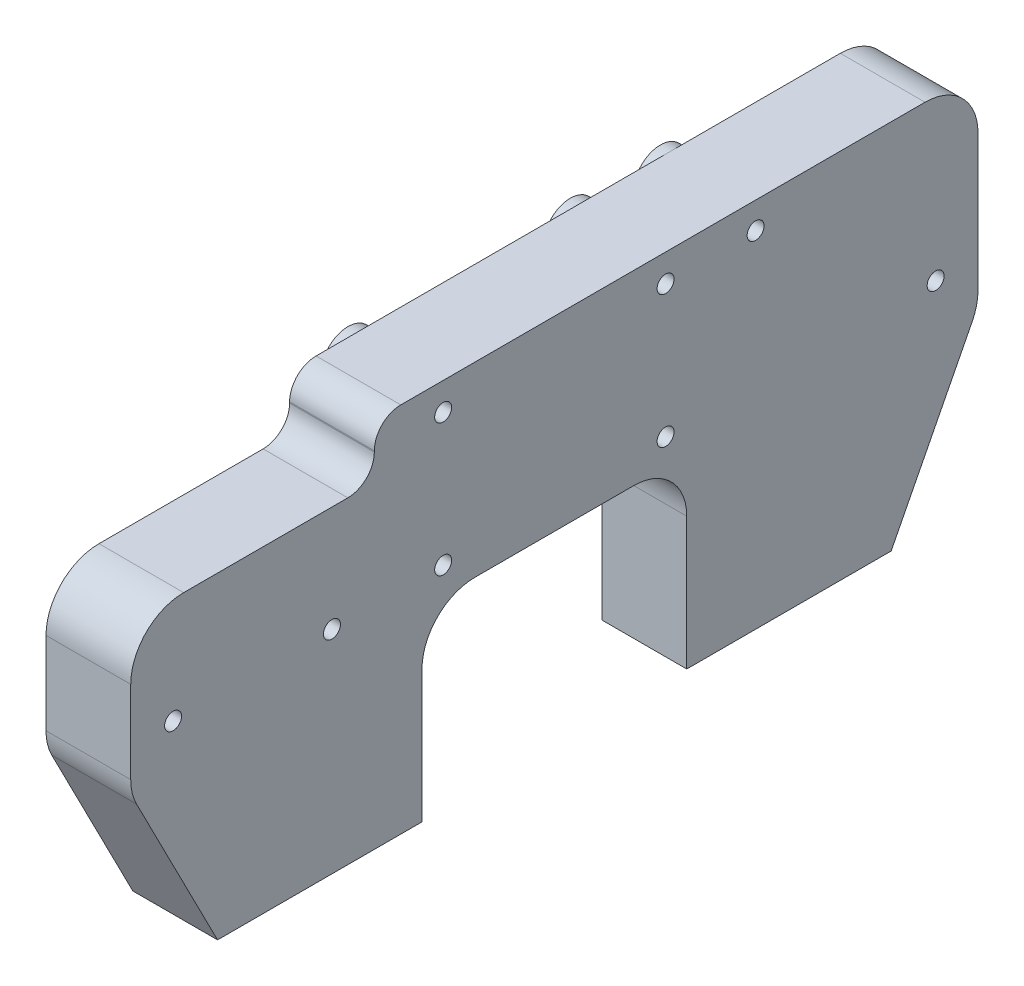
SolidWorks part; units mm, degrees
ref_plane "Front Plane" through (0, 0, 0) normal (0, 0, 1) x (1, 0, 0)
ref_plane "Top Plane" through (0, 0, 0) normal (0, 1, 0) x (1, 0, 0)
ref_plane "Right Plane" through (0, 0, 0) normal (1, 0, 0) x (0, 0, -1)
sketch "Sketch2" plane through (0, 0, 0) normal (1, 0, 0) x (0, 0, -1)
  line L0 (-40, 0) -> (-40, 40)
  line L1 (-40, 40) -> (40, 40)
  line L2 (40, 40) -> (40, 0)
  line L3 (40, 0) -> (-40, 0)
  point P4 (0, 0)
  dimension "D1" = 80
  dimension "D2" = 40
extrude "Boss-Extrude1" add sketch "Sketch2" along normal blind 8
sketch "Sketch3" plane through (8, 0, 0) normal (1, 0, 0) x (0, 0, -1)
  line L0 (-40, 40) -> (-40, 0) construction
  line L1 (-38.5, 17.5) -> (-18.5, 17.5) construction
  line L2 (-38.5, 17.5) -> (-38.5, 35.5) construction
  line L3 (-38.5, 35.5) -> (-18.5, 35.5) construction
  line L4 (-18.5, 17.5) -> (-18.5, 35.5) construction
  line L5 (-40, 0) -> (40, 0) construction
  circle A0 centre (-36, 20) radius 2.5
  circle A1 centre (-21, 20) radius 2.5
  point P4 (-28.5, 17.5)
  dimension "D1" = 5
  dimension "D2" = 5
  dimension "D3" = 15
  dimension "D4" = 20
  dimension "D5" = 18
  dimension "D6" = 7.5
  dimension "D7" = 2.5
  dimension "D8" = 4
  dimension "D9" = 20
extrude "Boss-Extrude2" add sketch "Sketch3" against normal blind 9 contours A0 | A1 region at (8, 20, 36) region at (8, 20, 21)
sketch "Sketch4" plane through (8, 0, 0) normal (1, 0, 0) x (0, 0, -1)
  line L0 (-40, 0) -> (40, 0) construction
  line L1 (16.5, 17.5) -> (38.5, 17.5)
  line L2 (16.5, 17.5) -> (16.5, 37.4)
  line L3 (16.5, 37.4) -> (38.5, 37.4)
  line L4 (38.5, 17.5) -> (38.5, 37.4)
  circle A0 centre (36, 20) radius 2.5
  circle A1 centre (19, 32.6) radius 2.5
  dimension "D1" = 5
  dimension "D2" = 5
  dimension "D3" = 12.6
  dimension "D4" = 17
  dimension "D5" = 19.9
  dimension "D6" = 22
  dimension "D7" = 20
extrude "Boss-Extrude3" add sketch "Sketch4" against normal blind 9 contours A0 | A1 region at (8, 32.6, -19) region at (8, 20, -36)
sketch "Sketch5" plane through (8, 0, 0) normal (1, 0, 0) x (0, 0, -1)
  line L1 (-12.5, 18) -> (12.5, 18) construction
  line L2 (-12.5, 18) -> (-12.5, 42) construction
  line L3 (-12.5, 42) -> (12.5, 42) construction
  line L4 (12.5, 18) -> (12.5, 42) construction
  line L5 (-40, 0) -> (40, 0) construction
  line L8 (40, 40) -> (-40, 40) construction
  circle A0 centre (-10.5, 20) radius 2.5
  circle A1 centre (10.5, 20) radius 2.5
  circle A2 centre (10.5, 32.5) radius 2.5
  circle A3 centre (-10.5, 32.5) radius 2.5
  point P3 (0, 42)
  point P17 (0, 40)
  dimension "D1" = 5
  dimension "D4" = 21
  dimension "D5" = 12.5
  dimension "D6" = 24
  dimension "D7" = 25
  dimension "D8" = 2
  dimension "D9" = 2
  dimension "D10" = 20
  dimension "D2" = 2
  dimension "D3" = 2
extrude "Boss-Extrude4" add sketch "Sketch5" against normal blind 9
sketch "Sketch7" plane through (8, 0, 0) normal (1, 0, 0) x (0, 0, -1)
  line L0 (-31.8, 0) -> (-40, 16)
  line L1 (-40, 0) -> (40, 0) construction
  line L2 (-40, 40) -> (-40, 0) construction
  line L3 (-40, 16) -> (-47.0872, 13.4851)
  line L4 (-47.0872, 13.4851) -> (-40, -21.9083)
  line L5 (-40, -21.9083) -> (60.4332, -20.413)
  line L6 (60.4332, -20.413) -> (53.6454, 13.4851)
  line L7 (53.6454, 13.4851) -> (40, 16)
  line L8 (40, 0) -> (40, 40) construction
  line L9 (40, 16) -> (31.8, 0)
  line L10 (-31.8, 0) -> (-12.5, 0)
  line L11 (-12.5, 0) -> (-12.5, 17.5)
  line L12 (-12.5, 17.5) -> (12.5, 17.5)
  line L13 (12.5, 17.5) -> (12.5, 0)
  line L14 (12.5, 0) -> (31.8, 0)
  line L15 (-40, 30) -> (-17, 30)
  line L16 (-17, 35.1) -> (-17, 30)
  line L17 (-17, 56.378) -> (-45.8801, 54.4436)
  line L18 (-45.8801, 54.4436) -> (-40, 30)
  line L19 (40, 35.1) -> (-17, 35.1)
  line L20 (-17, 44.251) -> (-17, 56.378)
  line L21 (-17, 44.251) -> (58.9628, 50.4661)
  line L22 (58.9628, 50.4661) -> (40, 35.1)
  circle A0 centre (-36, 20) radius 2.5 construction
  circle A1 centre (10.5, 20) radius 2.5 construction
  circle A2 centre (-21, 20) radius 2.5 construction
  circle A3 centre (19, 32.6) radius 2.5 construction
  point P15 (0, 17.5)
  point P22 (0, 0)
  dimension "D1" = 63.6
  dimension "D2" = 4
  dimension "D3" = 25
  dimension "D4" = 2.5
  dimension "D5" = 10
  dimension "D8" = 2.5
extrude "Cut-Extrude1" cut sketch "Sketch7" against normal through all
ref_plane "Plane1" through (4, 0, 0) normal (1, 0, 0) x (0, 0, -1)
fillet "Fillet5" radius 5 6 edges at (4, 16, -40) (4, 35.1, -40) (4, 30, 40) (4, 16, 40) (4, 17.5, -12.5) (4, 17.5, 12.5)
fillet "Fillet6" radius 2.5 2 edges at (4, 35.1, 17) (4, 30, 17)
sketch "Sketch8" plane through (0, 0, 0) normal (0, 1, 0) x (1, 0, 0)
  line L0 (8, -35) -> (8, -19.5) construction
  line L1 (8, -28) -> (16, -28)
  line L2 (8, -28) -> (8, -20)
  line L3 (8, -20) -> (16, -20)
  line L4 (16, -28) -> (16, -20)
  line L10 (8, -14.5) -> (8, 35) construction
  line L11 (8, 28) -> (16, 28)
  line L12 (8, 28) -> (8, 20)
  line L13 (8, 20) -> (16, 20)
  line L14 (16, 28) -> (16, 20)
  dimension "D1" = 56
  dimension "D2" = 20
  dimension "D3" = 8
  dimension "D4" = 8
extrude "Boss-Extrude5" add sketch "Sketch8" along normal blind 4 contours L14 L11 L12 L13 | L1 L4 L3 L2
fillet "Fillet7" radius 3.9 4 edges at (16, 2, 28) (16, 2, 20) (16, 2, -20) (16, 2, -28)
hole_wizard "M3 Clearance Hole1" positions "Sketch9" profile "Sketch10" hole size "M3" standard "ANSI Metric" end condition through all
sketch "Sketch9" plane through (0, 4, 0) normal (0, 1, 0) x (1, 0, 0)
  point P0 (12, -24)
  point P2 (-4, -24)
  point P4 (-4, 24)
  point P6 (12, 24)
  dimension "D1" = 16
  dimension "D2" = 4
  dimension "D3" = 24
  dimension "D4" = 48
sketch "Sketch10" plane through (12, 4, 24) normal (1, 0, 0) x (0, 0, 1)
  line L0 (0, 0) -> (0, 4)
  line L1 (0, 4) -> (1.7, 4)
  line L2 (1.7, 4) -> (1.7, 0)
  line L5 (1.7, 0) -> (0, 0)
  line L11 (0, -6.35) -> (0, 107.95) construction
  dimension "Thru Hole Dia." = 3.4
  dimension "Thru Hole Depth" = 4
hole_wizard "M2x0.4 Tapped Hole1" positions "Sketch11" profile "Sketch12" tap size "M2x0.4" standard "ANSI Metric" end condition through all
sketch "Sketch11" plane through (-1, 0, 0) normal (-1, 0, 0) x (0, 0, 1)
  circle A0 centre (10.5, 32.5) radius 2.5 construction
  circle A1 centre (10.5, 20) radius 2.5 construction
  circle A2 centre (21, 20) radius 2.5 construction
  circle A3 centre (36, 20) radius 2.5 construction
  circle A4 centre (-10.5, 20) radius 2.5 construction
  circle A5 centre (-10.5, 32.5) radius 2.5 construction
  circle A6 centre (-19, 32.6) radius 2.5 construction
  circle A7 centre (-36, 20) radius 2.5 construction
  point P0 (-19, 32.6)
  point P2 (-36, 20)
  point P4 (-10.5, 32.5)
  point P6 (-10.5, 20)
  point P8 (10.5, 20)
  point P10 (10.5, 32.5)
  point P12 (21, 20)
  point P14 (36, 20)
sketch "Sketch12" plane through (-1, 32.6, -19) normal (0, 1, 0) x (0, 0, 1)
  line L0 (0, 0) -> (0, 17)
  line L1 (0, 17) -> (0.8, 17)
  line L2 (0.8, 17) -> (0.8, 0)
  line L5 (0.8, 0) -> (0, 0)
  line L11 (0, -6.35) -> (0, 107.95) construction
  dimension "Thru Tap Drill Dia." = 1.6
  dimension "Thru Tap Drill Depth" = 17
cosmetic thread "Hole Thread9" parameters "D2"=2
cosmetic thread "Hole Thread10" parameters "D2"=2
cosmetic thread "Hole Thread11" parameters "D2"=2
cosmetic thread "Hole Thread12" parameters "D2"=2
cosmetic thread "Hole Thread13" parameters "D2"=2
cosmetic thread "Hole Thread14" parameters "D2"=2
cosmetic thread "Hole Thread15" parameters "D2"=2
cosmetic thread "Hole Thread16" parameters "D2"=2
mirror "Mirror1" about plane through (4, 0, 0) normal (1, 0, 0) of "M3 Clearance Hole1", "Fillet7", "Boss-Extrude5"
sketch "Sketch13" plane through (0, 0, 0) normal (0, 1, 0) x (1, 0, 0)
  line L1 (8, -31.8) -> (26.8959, -31.8)
  line L2 (8, -31.8) -> (8, 32.868)
  line L3 (8, 32.868) -> (26.8959, 32.868)
  line L4 (26.8959, -31.8) -> (26.8959, 32.868)
extrude "Cut-Extrude2" cut sketch "Sketch13" along normal blind 10
